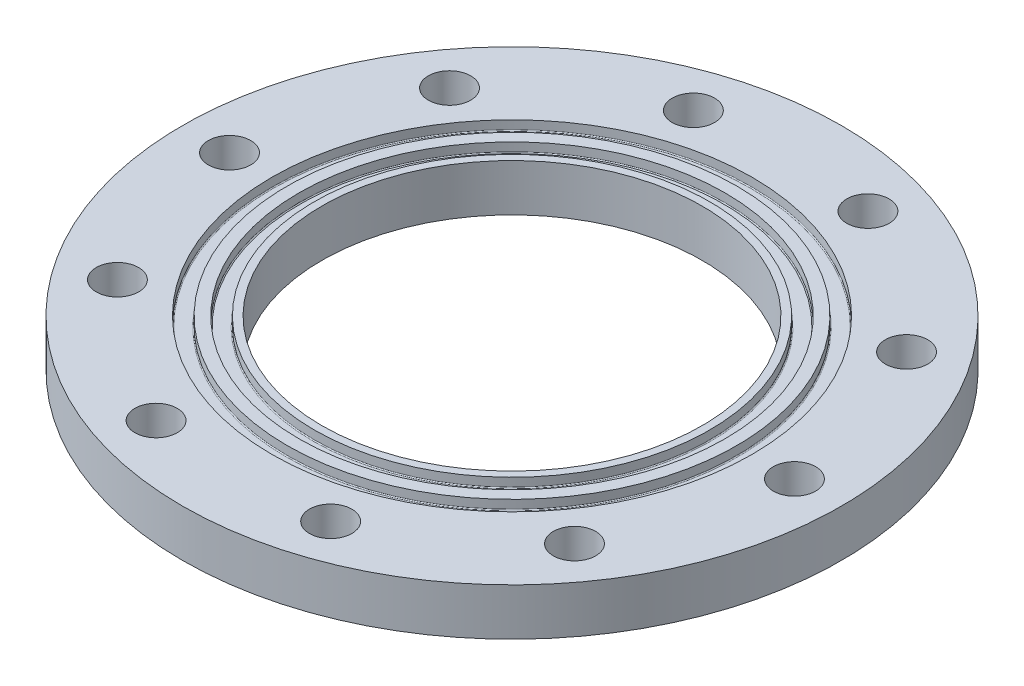
SolidWorks part; units mm, degrees
ref_plane "Front Plane" through (0, 0, 0) normal (0, 0, 1) x (1, 0, 0)
ref_plane "Top Plane" through (0, 0, 0) normal (0, 1, 0) x (1, 0, 0)
ref_plane "Right Plane" through (0, 0, 0) normal (1, 0, 0) x (0, 0, -1)
sketch "Sketch1" plane through (0, 0, 0) normal (0, 1, 0) x (1, 0, 0)
  circle A0 centre (0, 0) radius 40.4
  circle A9 centre (0, 0) radius 70
  circle A10 centre (0, 0) radius 47.4 construction
  dimension "D1" = 80.8
  dimension "D7" = 94.8
  dimension "D6" = 140
extrude "Boss-Extrude3" add sketch "Sketch1" along normal blind 10 contours A0 | A9 | A0 region at (-68.0201, 0, 0)
sketch "Sketch6" plane through (0, 0, 0) normal (1, 0, 0) x (0, 0, -1)
  line L0 (0, -6.7559) -> (0, 9.1132) construction
sketch "Sketch7" plane through (0, 0, 0) normal (0, 1, 0) x (1, 0, 0)
  line L0 (-47.4, 0) -> (-70, 0) construction
  circle A3 centre (-60, 0) radius 4.5
  circle A4 centre (0, 0) radius 47.4 construction
  circle A5 centre (0, 0) radius 70 construction
  dimension "D1" = 9
  dimension "D2" = 60
extrude "Cut-Extrude8" cut sketch "Sketch7" along normal through all
pattern_circular "CirPattern1" count 10 over 360 about axis through (0, -6.7559, 0) along (0, 1, 0) of "Cut-Extrude8"
sketch "Sketch9" plane through (0, 10, 0) normal (0, 1, 0) x (1, 0, 0)
  circle A0 centre (0, 0) radius 42
  circle A1 centre (0, 0) radius 45.25
  circle A2 centre (0, 0) radius 47.75
  circle A3 centre (0, 0) radius 51
  dimension "D1" = 84
  dimension "D2" = 3.25
  dimension "D3" = 95.5
  dimension "D4" = 3.25
extrude "Cut-Extrude9" cut sketch "Sketch9" against normal blind 2 contours A3 A2 | A1 A0 region at (-43.9701, 10, 0) region at (-49.5575, 10, 0)
fillet "Fillet1" radius 0.2 4 edges at (0, 8, 45.25) (0, 8, 42) (0, 8, 51) (0, 8, 47.75)
